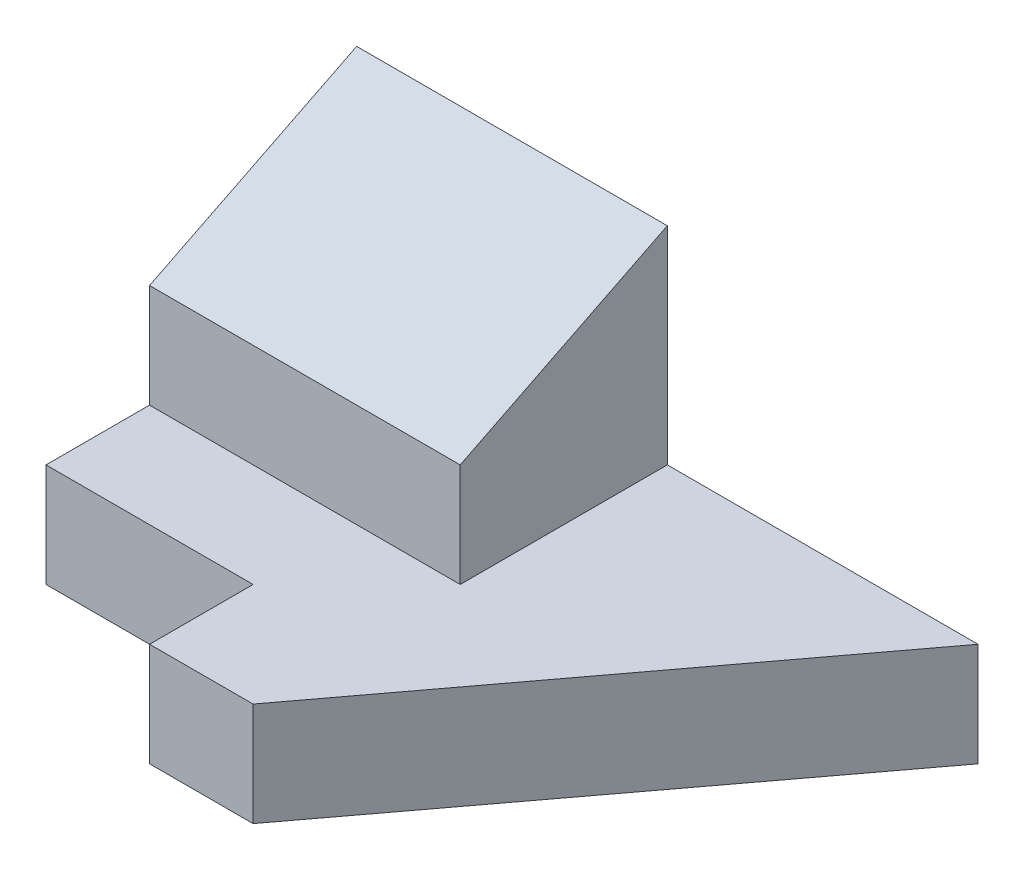
SolidWorks part; units mm, degrees
ref_plane "前基準面" through (0, 0, 0) normal (0, 0, 1) x (1, 0, 0)
ref_plane "上基準面" through (0, 0, 0) normal (0, 1, 0) x (1, 0, 0)
ref_plane "右基準面" through (0, 0, 0) normal (1, 0, 0) x (0, 0, -1)
sketch "草圖1" plane through (0, 0, 0) normal (0, 1, 0) x (1, 0, 0)
  line L0 (0, -10) -> (15, 10)
  line L1 (-5, -10) -> (0, -10)
  line L2 (-15, -5) -> (-15, 10)
  line L3 (-15, 10) -> (15, 10)
  line L5 (-15, -10) -> (15, 10) construction
  line L6 (-15, 10) -> (5, -3.3333) construction
  line L9 (-15, -5) -> (-5, -5)
  line L10 (-5, -10) -> (-5, -5)
  line L11 (-15, 10) -> (0, 10)
  line L12 (-15, 10) -> (-15, 0)
  line L13 (-15, 0) -> (0, 0)
  line L14 (0, 10) -> (0, 0)
  point P0 (0, 0)
  dimension "D1" = 20
  dimension "D4" = 5
  dimension "D5" = 10
  dimension "D6" = 15
  dimension "D7" = 10
extrude "填料-伸長1" add sketch "草圖1" along normal blind 5 contours L3 L14 L13 L2 L9 L10 L1 L0 | L14 L3 L2 L13 region at (0.5, 0, -0.5) region at (-7.5, 0, -5)
extrude "填料-伸長2" add sketch "草圖1<3>" along normal blind 15 contours L14 L3 L2 L13 region at (-7.5, 0, -5)
sketch "草圖1<3>" plane through (0, 0, 0) normal (0, 1, 0) x (1, 0, 0) same geometry as "草圖1"
sketch "草圖2" plane through (0, 0, 0) normal (1, 0, 0) x (0, 0, -1)
  line L0 (10, 15) -> (0, 10)
  line L1 (0, 15) -> (0, 5) construction
  line L2 (0, 10) -> (0, 15)
  line L3 (0, 15) -> (10, 15)
  dimension "D1" = 5
extrude "除料-伸長1" cut sketch "草圖2" against normal blind 15
scale "縮放比例1" scale about centroid uniform scaling yes scale factor 0.2
